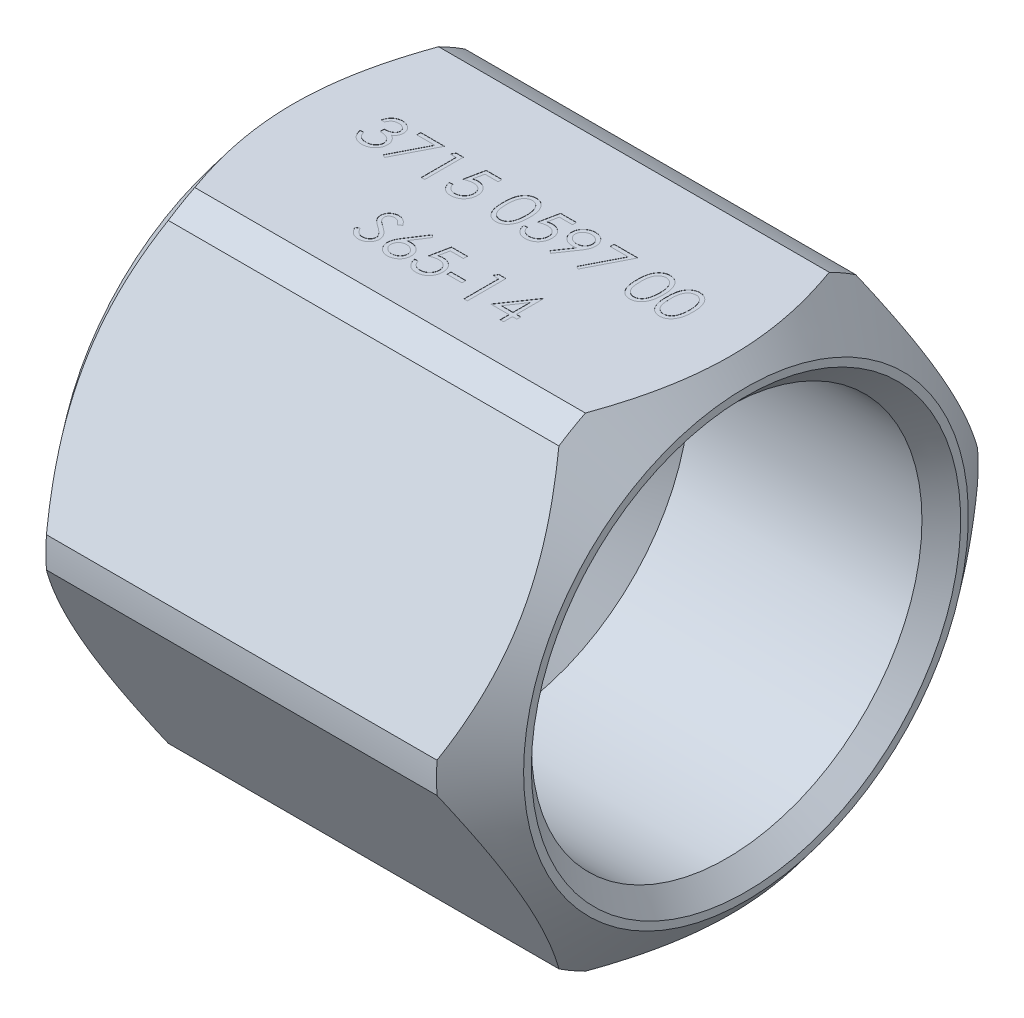
SolidWorks part; units mm, degrees
material "4140 H/T"
ref_plane "Front Plane" through (0, 0, 0) normal (0, 0, 1) x (1, 0, 0)
ref_plane "Top Plane" through (0, 0, 0) normal (0, 1, 0) x (1, 0, 0)
ref_plane "Right Plane" through (0, 0, 0) normal (1, 0, 0) x (0, 0, -1)
sketch "Sketch1" plane through (0, 0, 0) normal (0, 0, 1) x (1, 0, 0)
  line L0 (0, 0) -> (32.0688, 0) construction
  line L1 (0, 0) -> (0, 11.5)
  line L2 (0, 11.5) -> (2, 14)
  line L3 (2, 14) -> (22.2, 14)
  line L4 (22.2, 14) -> (24.2, 11.5)
  line L5 (24.2, 11.5) -> (24.2, 10.1)
  line L6 (24.2, 10.1) -> (11.2, 10.1)
  line L7 (11.2, 10.1) -> (7.2043, 5)
  line L9 (0, 0) -> (4.2, 0)
  line L11 (7.2043, 5) -> (4.2, 0)
  dimension "D1" = 10
  dimension "D2" = 20
  dimension "D3" = 24.2
  dimension "D4" = 23
  dimension "D5" = 28
  dimension "D7" = 2
  dimension "D6" = 2
  dimension "D8" = 20.2
  dimension "D9" = 13
  dimension "D10" = 59
revolve "Revolve1" add sketch "Sketch1" angle 360 about L0
sketch "Sketch2" plane through (24.2, 0, 0) normal (1, 0, 0) x (0, 0, -1)
  line L1 (7.2169, 12.5) -> (-7.2169, 12.5)
  line L2 (-7.2169, 12.5) -> (-14.4338, 0)
  line L3 (-14.4338, 0) -> (-7.2169, -12.5)
  line L4 (-7.2169, -12.5) -> (7.2169, -12.5)
  line L5 (7.2169, -12.5) -> (14.4338, 0)
  line L6 (14.4338, 0) -> (7.2169, 12.5)
  circle A0 centre (0, 0) radius 12.5 construction
  dimension "D1" = 25
extrude "Extrude1" cut sketch "Sketch2" against normal up to surface (24.2 mm away) flip side to cut up to face at (0, 0, 11.5)
chamfer "Chamfer1" distance 1 angle 45 1 edges at (24.2, 0, 10.1)
sketch "Sketch3" plane through (0, 12.5, 0) normal (0, 1, 0) x (1, 0, 0)
  line L0 (0, 0) -> (24.2, 0) construction
  line L1 (24.2, -11.5) -> (24.2, 11.5) construction
  text T0 "3715 0597 00\r\nS65-14" font "Century Gothic" height 2
extrude "Cut-Extrude1" cut sketch "Sketch3" against normal blind 0.01
